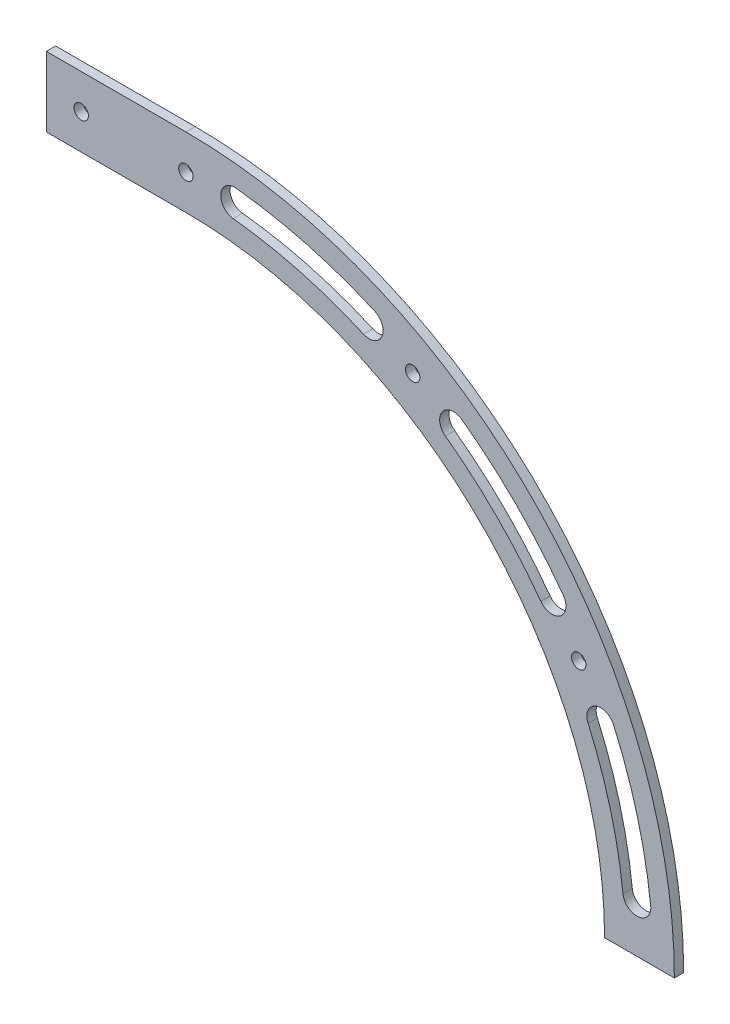
SolidWorks part; units mm, degrees
material "Thornel Mat VMA"
ref_plane "前视基准面" through (0, 0, 0) normal (0, 0, 1) x (1, 0, 0)
ref_plane "上视基准面" through (0, 0, 0) normal (0, 1, 0) x (1, 0, 0)
ref_plane "右视基准面" through (0, 0, 0) normal (1, 0, 0) x (0, 0, -1)
other "Configuration Table"
sketch "草图1" plane through (0, 0, 0) normal (0, 0, 1) x (1, 0, 0)
  line L0 (0, 105) -> (0, 0) construction
  line L1 (0, 0) -> (105, 0) construction
  line L2 (90, 0) -> (105, 0)
  line L3 (0, 105) -> (0, 90)
  arc A0 (0, 105) -> (105, 0) centre (0, 0) cw
  arc A1 (0, 90) -> (90, 0) centre (0, 0) cw
  dimension "D1" = 105
  dimension "D2" = 90
extrude "凸台-拉伸1" add sketch "草图1" along normal blind 15
sketch "草图2" plane through (0, 0, 0) normal (0, -1, 0) x (1, 0, 0)
  line L1 (90, 15) -> (105, 15)
  line L2 (90, 15) -> (90, 0)
  line L3 (90, 0) -> (105, 0)
  line L4 (105, 15) -> (105, 0)
extrude "凸台-拉伸2" add sketch "草图2" along normal blind 5
sketch "草图3" plane through (105, 0, 0) normal (1, 0, 0) x (0, 0, -1)
  line L0 (0, -5) -> (50, -5) construction
  line L1 (50, -5) -> (50, -55) construction
  line L2 (50, -55) -> (50, -70)
  line L3 (-15, -5) -> (0, -5)
  arc A0 (0, -5) -> (50, -55) centre (50, -5) ccw
  arc A1 (-15, -5) -> (50, -70) centre (50, -5) ccw
  dimension "D1" = 50
extrude "凸台-拉伸3" add sketch "草图3" against normal blind 15
sketch "草图4" plane through (0, 0, 15) normal (0, 0, 1) x (1, 0, 0)
  line L0 (25.2349, 94.1778) -> (0, 0) construction
  line L1 (0, 0) -> (68.9429, 68.9429) construction
  line L2 (0, 0) -> (94.1778, 25.2349) construction
  line L3 (0, 0) -> (90, 0) construction
  line L4 (48.75, 84.4375) -> (0, 0) construction
  line L5 (84.4375, 48.75) -> (0, 0) construction
  arc A0 (10.4903, 96.934) -> (39.3822, 89.1925) centre (0, 0) cw construction
  arc A1 (40.5939, 91.9368) -> (10.813, 99.9166) centre (0, 0) ccw
  arc A2 (38.1704, 86.4481) -> (10.1675, 93.9514) centre (0, 0) ccw
  arc A3 (38.1704, 86.4481) -> (40.5939, 91.9368) centre (39.3822, 89.1925) ccw
  arc A4 (10.813, 99.9166) -> (10.1675, 93.9514) centre (10.4903, 96.934) ccw
  arc A5 (57.5518, 78.7022) -> (78.7022, 57.5518) centre (0, 0) cw construction
  arc A6 (81.1238, 59.3227) -> (59.3227, 81.1238) centre (0, 0) ccw
  arc A7 (76.2806, 55.781) -> (55.781, 76.2806) centre (0, 0) ccw
  arc A8 (76.2806, 55.781) -> (81.1238, 59.3227) centre (78.7022, 57.5518) ccw
  arc A9 (59.3227, 81.1238) -> (55.781, 76.2806) centre (57.5518, 78.7022) ccw
  arc A10 (89.1925, 39.3822) -> (96.934, 10.4903) centre (0, 0) cw construction
  arc A11 (99.9166, 10.813) -> (91.9368, 40.5939) centre (0, 0) ccw
  arc A12 (93.9514, 10.1675) -> (86.4481, 38.1704) centre (0, 0) ccw
  arc A13 (93.9514, 10.1675) -> (99.9166, 10.813) centre (96.934, 10.4903) ccw
  arc A14 (91.9368, 40.5939) -> (86.4481, 38.1704) centre (89.1925, 39.3822) ccw
  circle A17 centre (84.4375, 48.75) radius 1.55
  circle A18 centre (48.75, 84.4375) radius 1.55
  point P4 (25.2349, 94.1778)
  point P9 (68.9429, 68.9429)
  point P18 (94.1778, 25.2349)
  dimension "D1" = 3
  dimension "D2" = 3
  dimension "D3" = 3
  dimension "D7" = 97.5
  dimension "D8" = 97.5
  dimension "D9" = 97.5
  dimension "D12" = 3.1
  dimension "D13" = 3.1
  dimension "D14" = 15
  dimension "D4" = 15
  dimension "D5" = 45
  dimension "D6" = 75
  dimension "D10" = 97.5
  dimension "D11" = 97.5
  dimension "D15" = 15
  dimension "D16" = 15
  dimension "D17" = 15
  dimension "D18" = 15
sketch "草图5" plane through (105, 0, 0) normal (1, 0, 0) x (0, 0, -1)
  line L0 (-2.1127, -29.3006) -> (50, -5) construction
  line L1 (50, -5) -> (25.6994, -57.1127) construction
  line L2 (50, -55) -> (50, -5) construction
  line L3 (50, -5) -> (0, -5) construction
  line L4 (-7.2812, -10.0115) -> (50, -5) construction
  line L5 (50, -5) -> (9.3414, -45.6586) construction
  line L6 (50, -5) -> (44.9694, -62.5) construction
  arc A0 (-5.5348, -19.9043) -> (2.8856, -37.9618) centre (50, -5) ccw construction
  arc A1 (-8.4322, -20.6819) -> (0.4274, -39.6816) centre (50, -5) ccw
  arc A2 (-2.6373, -19.1267) -> (5.3437, -36.2421) centre (50, -5) ccw
  arc A3 (-2.6373, -19.1267) -> (-8.4322, -20.6819) centre (-5.5348, -19.9043) ccw
  arc A4 (0.4274, -39.6816) -> (5.3437, -36.2421) centre (2.8856, -37.9618) ccw
  arc A5 (17.0382, -52.1144) -> (35.0957, -60.5348) centre (50, -5) ccw construction
  arc A6 (15.3184, -54.5726) -> (34.3181, -63.4322) centre (50, -5) ccw
  arc A7 (18.7579, -49.6563) -> (35.8733, -57.6373) centre (50, -5) ccw
  arc A8 (18.7579, -49.6563) -> (15.3184, -54.5726) centre (17.0382, -52.1144) ccw
  arc A9 (34.3181, -63.4322) -> (35.8733, -57.6373) centre (35.0957, -60.5348) ccw
  circle A13 centre (44.9694, -62.5) radius 1.55
  circle A14 centre (9.3414, -45.6586) radius 1.55
  circle A15 centre (-7.2812, -10.0115) radius 1.55
  point P4 (-2.1127, -29.3006)
  point P9 (25.6994, -57.1127)
  dimension "D1" = 57.5
  dimension "D2" = 57.5
  dimension "D8" = 3.1
  dimension "D9" = 3.1
  dimension "D10" = 3.1
  dimension "D12" = 25
  dimension "D13" = 3
  dimension "D16" = 3
  dimension "D3" = 57.5
  dimension "D4" = 57.5
  dimension "D5" = 57.5
  dimension "D6" = 10
  dimension "D7" = 10
  dimension "D11" = 45
  dimension "D14" = 5
  dimension "D15" = 5
  dimension "D17" = 25
extrude "切除-拉伸1" cut sketch "草图4" against normal through all
extrude "切除-拉伸2" cut sketch "草图5" against normal through all
sketch "草图6" plane through (105, 0, 0) normal (1, 0, 0) x (0, 0, -1)
  line L0 (50, -55) -> (50, -70)
  line L1 (0, -5) -> (-15, -5)
  arc A0 (0, -5) -> (50, -55) centre (50, -5) ccw
  arc A1 (-15, -5) -> (50, -70) centre (50, -5) ccw
extrude "切除-拉伸3" cut sketch "草图6" against normal blind 4
sketch "草图7" plane through (0, 0, 15) normal (0, 0, 1) x (1, 0, 0)
  line L0 (0, 105) -> (0, 90)
  line L1 (90, 0) -> (105, 0)
  line L2 (90, -5) -> (90, 0) construction
  arc A0 (0, 90) -> (90, 0) centre (0, 0) cw
  arc A1 (0, 105) -> (105, 0) centre (0, 0) cw
extrude "切除-拉伸4" cut sketch "草图7" against normal through all flip side to cut
sketch "草图8" plane through (0, 0, 15) normal (0, 0, 1) x (1, 0, 0)
  line L0 (0, 105) -> (0, 90)
  line L1 (90, 0) -> (105, 0)
  arc A0 (0, 90) -> (90, 0) centre (0, 0) cw
  arc A1 (0, 105) -> (105, 0) centre (0, 0) cw
extrude "切除-拉伸5" cut sketch "草图8" against normal blind 13
sketch "草图9" plane through (0, 0, 2) normal (0, 0, 1) x (1, 0, 0)
  line L0 (0, 105) -> (0, 90) construction
  line L1 (0, 105) -> (-30, 105)
  line L2 (0, 105) -> (0, 90)
  line L3 (0, 90) -> (-30, 90)
  line L4 (-30, 105) -> (-30, 90)
  arc A0 (105, 0) -> (0, 105) centre (0, 0) ccw construction
  dimension "D1" = 15
  dimension "D2" = 30
extrude "凸台-拉伸4" add sketch "草图9" against normal up to surface (2 mm away) up to face at (25.026, 93.3983, 0)
sketch "草图10" plane through (0, 0, 2) normal (0, 0, 1) x (1, 0, 0)
  line L0 (0, 0) -> (0, 97.5) construction
  line L1 (-30, 90) -> (0, 90) construction
  line L2 (-30, 105) -> (-30, 90) construction
  circle A0 centre (0, 97.5) radius 1.55
  circle A1 centre (-22.5, 97.5) radius 1.55
  dimension "D2" = 3.1
  dimension "D5" = 3.1
  dimension "D1" = 7.5
  dimension "D3" = 7.5
  dimension "D4" = 7.5
extrude "切除-拉伸6" cut sketch "草图10" against normal through all
